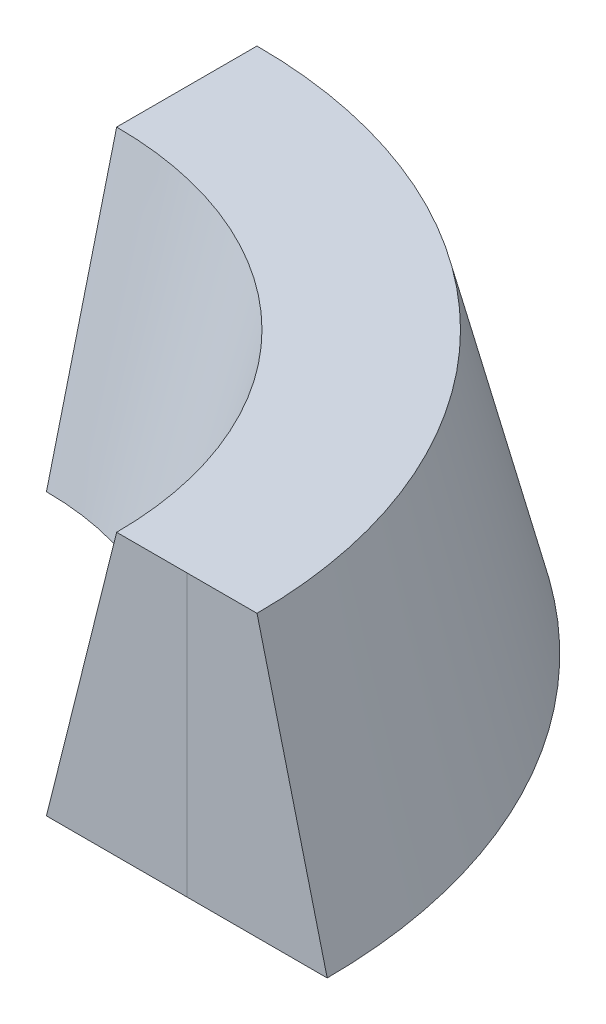
SolidWorks part; units mm, degrees
ref_plane "Front Plane" through (0, 0, 0) normal (0, 0, 1) x (1, 0, 0)
ref_plane "Top Plane" through (0, 0, 0) normal (0, 1, 0) x (1, 0, 0)
ref_plane "Right Plane" through (0, 0, 0) normal (1, 0, 0) x (0, 0, -1)
other "Configuration Table"
sketch "Sketch1" plane through (0, 0, 0) normal (0, 0, 1) x (1, 0, 0)
  line L0 (4000, 0) -> (8000, 0)
  line L1 (8000, 0) -> (7000, 4000)
  line L2 (7000, 4000) -> (5000, 4000)
  line L3 (5000, 4000) -> (4000, 0)
  dimension "D1" = 4000
  dimension "D2" = 8000
  dimension "D3" = 5000
  dimension "D4" = 7000
  dimension "D5" = 4000
sketch "Sketch3" plane through (0, 0, 0) normal (0, 0, 1) x (1, 0, 0)
  line L0 (0, 0) -> (0, 7261.7026)
ref_axis "Axis1" through (0, 0, 0) along (0, 1, 0)
revolve "Revolve1" add sketch "Sketch1" angle 90 about L0
sketch "Sketch7" plane through (0, 0, 0) normal (0, 0, 1) x (1, 0, 0)
  line L0 (6000, 0) -> (6000, 4000)
  line L1 (4000, 0) -> (8000, 0) construction
  line L2 (7000, 4000) -> (5000, 4000) construction
split line "Split Line1"
